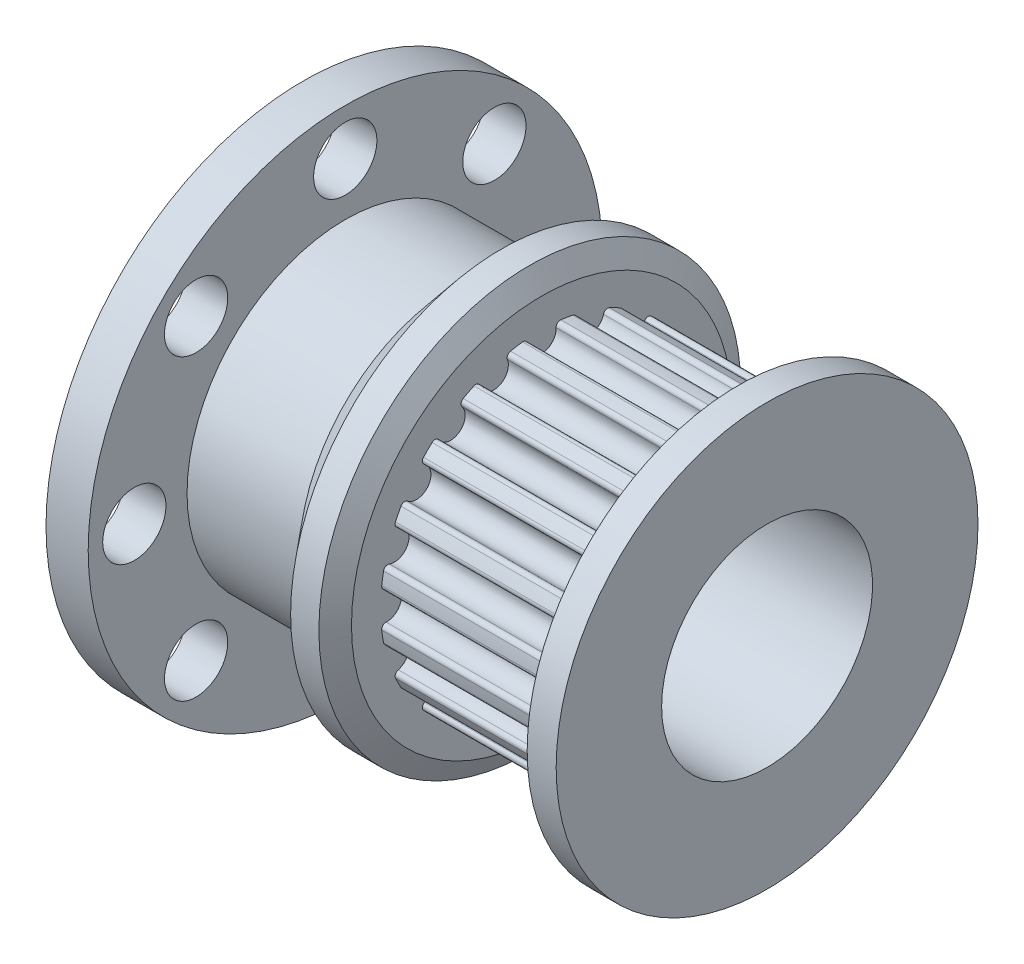
SolidWorks part; units mm, degrees
note: '?' marks a value the reader was unsure of.
other "Main_Body" parameters "D16"=0.5
material "6061-O (SS)"
ref_plane "Сверху" through (0, 0, 0) normal (0, 0, 1) x (1, 0, 0)
ref_plane "Справа" through (0, 0, 0) normal (0, 1, 0) x (1, 0, 0)
ref_plane "Спереди" through (0, 0, 0) normal (1, 0, 0) x (0, 0, -1)
sketch "Эскиз1" plane through (0, 0, 0) normal (0, 0, 1) x (1, 0, 0)
  line L0 (0, 0) -> (0, 6)
  line L1 (5.9282, 8) -> (4.25, 6)
  line L2 (5.9282, 8) -> (6.9997, 8)
  line L3 (6.9997, 8) -> (7.45, 7.2132)
  line L4 (7.45, 6.11) -> (14.45, 6.11)
  line L5 (14.45, 6.11) -> (14.45, 7.2132)
  line L6 (14.9003, 8) -> (16, 8)
  line L7 (16, 0) -> (16, 4.2314)
  line L8 (16, 4.2314) -> (15.8475, 4.3838)
  line L9 (15.8475, 4.3838) -> (16, 4.5363)
  line L10 (16, 4.5363) -> (16, 8)
  line L11 (0, 0) -> (16, 0)
  line L12 (7.45, 7.2132) -> (7.45, 6.11)
  line L13 (14.45, 7.2132) -> (14.9003, 8)
  line L16 (4.25, 6) -> (0, 6)
  dimension "D2" = 50
  dimension "D3" = 4.25
  dimension "D4" = 6
  dimension "D6" = 6.11
  dimension "D7" = 7.45
  dimension "D8" = 7
  dimension "D10" = 16
  dimension "D11" = 8
revolve "Body" add sketch "Эскиз1" angle 360 about L11
sketch "Эскиз2" plane through (16, 0, 0) normal (1, 0, 0) x (0, 0, -1)
  circle A0 centre (0, 0) radius 3.175
  dimension "D1" = 6.35
extrude "Bore" cut sketch "Эскиз2" against normal through all
sketch "Эскиз3" plane through (7.45, 0, 0) normal (1, 0, 0) x (0, 0, -1)
  line L0 (0, 0) -> (9.7637, 0) construction
  circle A0 centre (5.5827, -1.8139) radius 0.55
  circle A1 centre (0, 0) radius 6.42 construction
  circle A2 centre (4.7489, -3.4503) radius 0.55
  circle A3 centre (3.4503, -4.7489) radius 0.55
  circle A4 centre (1.8139, -5.5827) radius 0.55
  circle A5 centre (0, -5.87) radius 0.55
  circle A6 centre (5.87, 0) radius 0.55
  circle A7 centre (-1.8139, -5.5827) radius 0.55
  circle A8 centre (-3.4503, -4.7489) radius 0.55
  circle A9 centre (-4.7489, -3.4503) radius 0.55
  circle A10 centre (-5.5827, -1.8139) radius 0.55
  circle A11 centre (-5.87, 0) radius 0.55
  circle A12 centre (-5.5827, 1.8139) radius 0.55
  circle A13 centre (-4.7489, 3.4503) radius 0.55
  circle A14 centre (-3.4503, 4.7489) radius 0.55
  circle A17 centre (-1.8139, 5.5827) radius 0.55
  circle A18 centre (0, 5.87) radius 0.55
  circle A19 centre (1.8139, 5.5827) radius 0.55
  circle A20 centre (3.4503, 4.7489) radius 0.55
  circle A21 centre (4.7489, 3.4503) radius 0.55
  circle A22 centre (5.5827, 1.8139) radius 0.55
  point P45 (0, 0)
  dimension "D1" = 12.84
  dimension "D2" = 20
  dimension "D3" = 1.1
extrude "20T" cut sketch "Эскиз3" along normal blind 7
fillet "Fillet" radius 0.16 40 edges at (10.95, 0.5045, -6.0891) (10.95, -0.5045, -6.0891) (10.95, -1.4019, -5.947) (10.95, -2.3614, -5.6352) (10.95, -3.171, -5.2227) (10.95, -3.9872, -4.6297) (10.95, -4.6297, -3.9872) (10.95, -5.2227, -3.171) (10.95, -5.6352, -2.3614) (10.95, -5.947, -1.4019) (10.95, -6.0891, -0.5045) (10.95, -6.0891, 0.5045) (10.95, -5.947, 1.4019) (10.95, -5.6352, 2.3614) (10.95, -5.2227, 3.171) (10.95, -4.6297, 3.9872) (10.95, -3.9872, 4.6297) (10.95, -3.171, 5.2227) (10.95, -2.3614, 5.6352) (10.95, -1.4019, 5.947) (10.95, -0.5045, 6.0891) (10.95, 0.5045, 6.0891) (10.95, 1.4019, 5.947) (10.95, 2.3614, 5.6352) (10.95, 3.171, 5.2227) (10.95, 3.9872, 4.6297) (10.95, 4.6297, 3.9872) (10.95, 5.2227, 3.171) (10.95, 5.6352, 2.3614) (10.95, 5.947, 1.4019) (10.95, 6.0891, 0.5045) (10.95, 6.0891, -0.5045) (10.95, 5.947, -1.4019) (10.95, 5.6352, -2.3614) (10.95, 5.2227, -3.171) (10.95, 4.6297, -3.9872) (10.95, 3.9872, -4.6297) (10.95, 3.171, -5.2227) (10.95, 2.3614, -5.6352) (10.95, 1.4019, -5.947)
ref_axis "Axis1" through (0, 0, 0) along (1, 0, 0)?
sketch "Sketch4" plane through (0, 0, 0) normal (-1, 0, 0) x (0, 0, 1)
  circle A0 centre (0, 0) radius 9.75
extrude "Boss-Extrude3" add sketch "Sketch4" along normal blind 1.6
sketch "Sketch5" plane through (-1.6, 0, 0) normal (-1, 0, 0) x (0, 0, 1)
  circle A0 centre (0, 0) radius 4
  dimension "D1" = 8
extrude "Cut-Extrude3" cut sketch "Sketch5" against normal through all
sketch "Sketch11" plane through (-1.6, 0, 0) normal (-1, 0, 0) x (0, 0, 1)
  line L0 (0, 0) -> (8, 0) construction
  circle A0 centre (8, 0) radius 1.2
  dimension "D2" = 2.4
  dimension "D1" = 8
extrude "Cut-Extrude4" cut sketch "Sketch11" against normal up to next
pattern_circular "CirPattern1" count 8 every 45 about axis through (0, 0, 0) along (1, 0, 0) of "Cut-Extrude4"
sketch "Sketch12" plane through (16, 0, 0) normal (1, 0, 0) x (0, 0, -1)
  circle A0 centre (0, 0) radius 4.5363 construction
  circle A1 centre (0, 0) radius 4.5363
  circle A2 centre (0, 0) radius 4.2314 construction
  circle A3 centre (0, 0) radius 4.2314
extrude "Boss-Extrude4" add sketch "Sketch12" against normal up to surface (0.3049 mm away) contours A1
